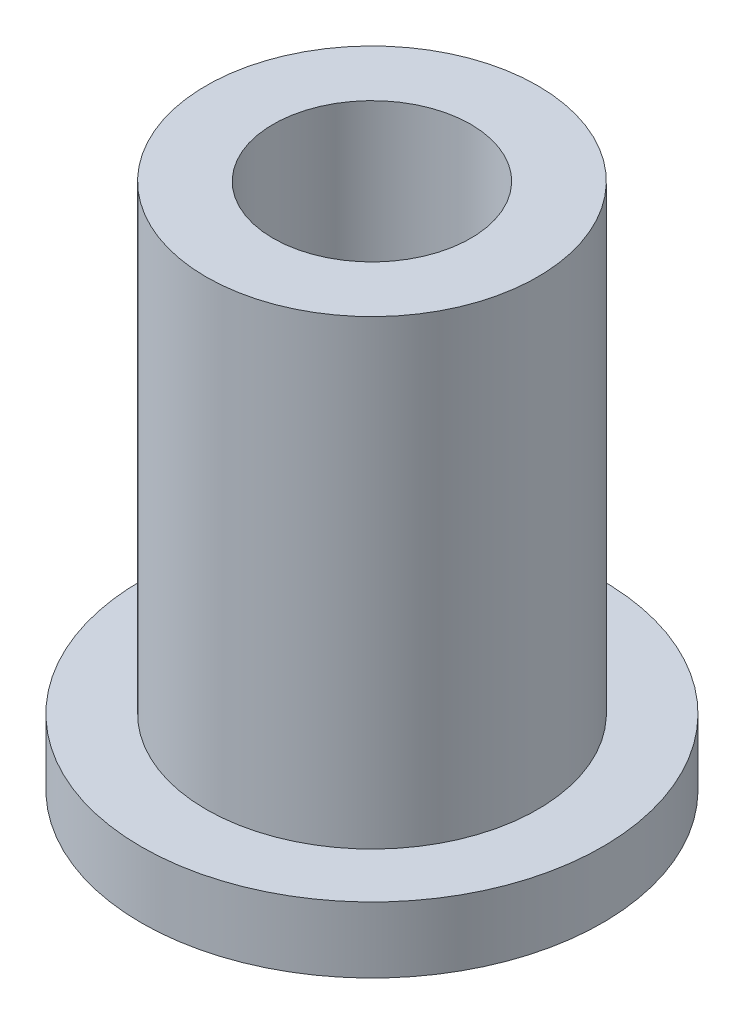
SolidWorks part; units mm, degrees
material "6061 Alloy"
ref_plane "Front Plane" through (0, 0, 0) normal (0, 0, 1) x (1, 0, 0)
ref_plane "Top Plane" through (0, 0, 0) normal (0, 1, 0) x (1, 0, 0)
ref_plane "Right Plane" through (0, 0, 0) normal (1, 0, 0) x (0, 0, -1)
sketch "Sketch1" plane through (0, 0, 0) normal (0, 1, 0) x (1, 0, 0)
  circle A0 centre (0, 0) radius 5.5562
  dimension "D1" = 11.1125
extrude "Boss-Extrude1" add sketch "Sketch1" along normal blind 1.5875
sketch "Sketch2" plane through (0, 1.5875, 0) normal (0, 1, 0) x (1, 0, 0)
  circle A1 centre (0, 0) radius 3.9942
  dimension "D2" = 7.9883
extrude "Boss-Extrude2" add sketch "Sketch2" along normal blind 11.1125 contours A1 region at (0, 1.5875, 0)
sketch "Sketch3" plane through (0, 12.7, 0) normal (0, 1, 0) x (1, 0, 0)
  circle A0 centre (0, 0) radius 2.3813
  dimension "D1" = 4.7625
extrude "Cut-Extrude1" cut sketch "Sketch3" against normal up to surface (12.7 mm away) contours A0 region at (0, 12.7, 0) up to face at (0, 0, 5.5562)
equation "\"D1@Boss-Extrude2\"=1/2-1/16"
